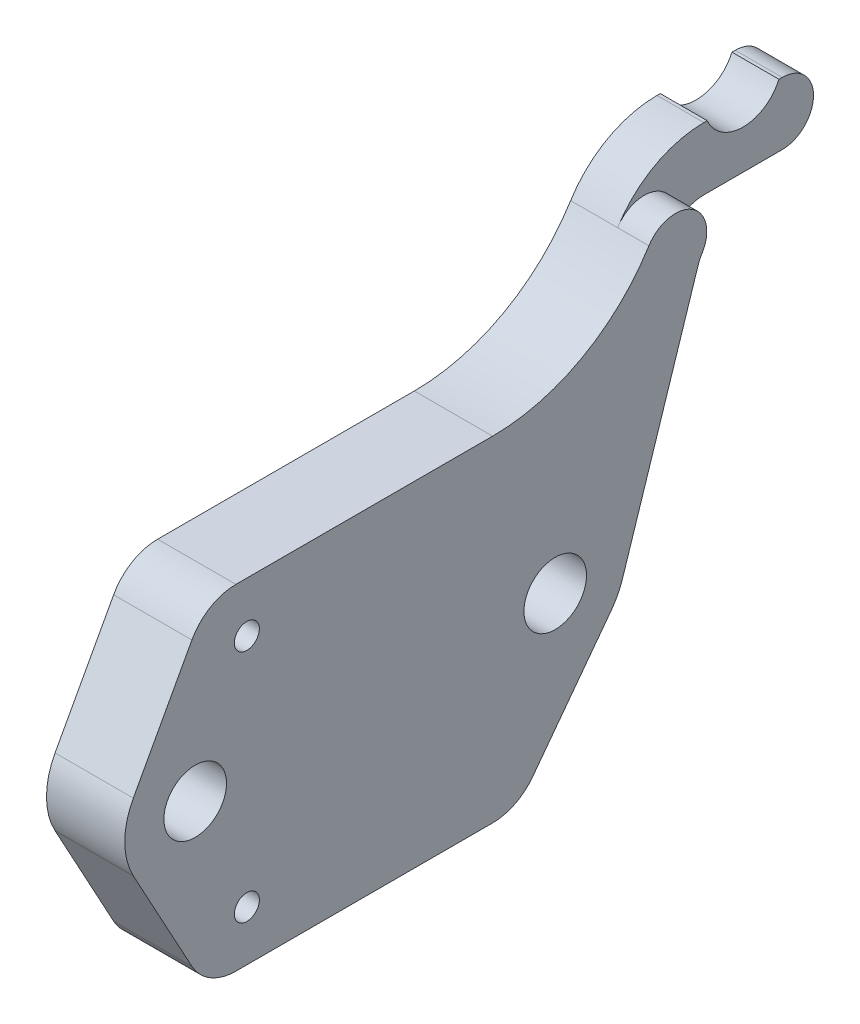
SolidWorks part; units mm, degrees
material "Alliage 1060"
ref_plane "Plan de face" through (0, 0, 0) normal (0, 0, 1) x (1, 0, 0)
ref_plane "Plan de dessus" through (0, 0, 0) normal (0, 1, 0) x (1, 0, 0)
ref_plane "Plan de droite" through (0, 0, 0) normal (1, 0, 0) x (0, 0, -1)
sketch "Esquisse1" plane through (0, 0, 0) normal (0, 0, 1) x (1, 0, 0)
  line L0 (0, 15) -> (0, -15) construction
  line L1 (-2.5, 15) -> (2.5, 15)
  line L2 (-2.5, 15) -> (-2.5, -15)
  line L3 (-2.5, -15) -> (2.5, -15)
  line L4 (2.5, 15) -> (2.5, -15)
  dimension "D1" = 5
  dimension "D2" = 30
extrude "Extrusion1" add sketch "Esquisse1" against normal blind 32.5
sketch "Esquisse2" plane through (2.5, 0, 0) normal (1, 0, 0) x (0, 0, -1)
  line L0 (4.5, -4.3) -> (27.5, -4.3) construction
  line L3 (32.5, -15) -> (0, -15) construction
  line L5 (0, -15) -> (0, 15) construction
  circle A0 centre (4.5, -4.3) radius 2
  circle A1 centre (27.5, -4.3) radius 2
  dimension "D2" = 4
  dimension "D6" = 4
  dimension "D1" = 23
  dimension "D4" = 4.5
  dimension "D5" = 10.7
extrude "Extrusion2" cut sketch "Esquisse2" against normal through all
hole_wizard "Trou taraudé M21" positions "Esquisse10" profile "Esquisse9" tap size "M2" standard "Iso" end condition through all
sketch "Esquisse10" plane through (2.5, 0, 0) normal (1, 0, 0) x (0, 0, -1)
  line L1 (7.8, 3.2) -> (22.8, 3.2)
  line L2 (7.8, 3.2) -> (7.8, -11.8)
  line L3 (7.8, -11.8) -> (22.8, -11.8)
  line L4 (22.8, 3.2) -> (22.8, -11.8)
  line L5 (27.5, -4.3) -> (22.8, -4.3) construction
  circle A0 centre (27.5, -4.3) radius 2 construction
  point P2 (7.8, 3.2)
  point P100 (7.8, -11.8)
  dimension "D1" = 4.7
  dimension "D2" = 15
sketch "Esquisse9" plane through (2.5, 3.2, -7.8) normal (0, 1, 0) x (0, 0, -1)
  line L0 (0, 0) -> (0, 5)
  line L1 (0, 5) -> (0.8, 5)
  line L2 (0.8, 5) -> (0.8, 0)
  line L5 (0.8, 0) -> (0, 0)
  line L11 (0, -6.35) -> (0, 107.95) construction
  dimension "Diamètre du trou pour taraudage jusqu'au prochain" = 1.6
  dimension "Profondeur du trou pour taraudage jusqu'au prochain" = 5
cosmetic thread "Filetage de perçage12" parameters "D2"=2
cosmetic thread "Filetage de perçage13" parameters "D2"=2
sketch "Esquisse14" plane through (-2.5, 0, 0) normal (-1, 0, 0) x (0, 0, 1)
  line L0 (-32.5, 15) -> (-39.2087, 15)
  line L1 (-44, 11) -> (-39, 11)
  line L2 (-36.5348, 8.9159) -> (-32.5, -15)
  line L3 (-32.5, 15) -> (-32.5, -15) construction
  line L4 (-32.5, 15) -> (-32.5, -15)
  line L5 (-43.7913, 15) -> (-44, 15)
  arc A0 (-44, 15) -> (-44, 11) centre (-44, 13) ccw
  arc A1 (-39, 11) -> (-36.5348, 8.9159) centre (-39, 8.5) cw
  arc A2 (-43.7913, 15) -> (-39.2087, 15) centre (-41.5, 16) ccw
  dimension "D3" = 2.5
  dimension "D5" = 2.5
  dimension "D1" = 4
  dimension "D2" = 11.5
  dimension "D4" = 6.5
  dimension "D6" = 2.5
  dimension "D7" = 9
extrude "Boss.-Extru.2" add sketch "Esquisse14" against normal up to surface (5 mm away) up to face at (2.5, 3.2, -8.6)
sketch "Esquisse16" plane through (-2.5, 0, 0) normal (-1, 0, 0) x (0, 0, 1)
  line L0 (0, 15) -> (0, -15) construction
  line L1 (-23.5, -11.8) -> (-7.1, -11.8) construction
  line L2 (-39.2087, 15) -> (0, 15) construction
  line L3 (-32.5, -15) -> (0, -15) construction
  line L4 (-7.1, -11.8) -> (-7.1, 3.2) construction
  line L5 (-7.1, 3.2) -> (-23.5, 3.2) construction
  line L6 (-23.5, 3.2) -> (-23.5, -11.8) construction
  line L7 (0, -4.3) -> (0, -15)
  line L8 (0, -15) -> (-7.1, -15)
  line L9 (-23.5, -15) -> (-32.5, -15)
  line L10 (-32.5, -15) -> (-36.5348, 8.9159)
  line L11 (-39.2087, 15) -> (0, 15) construction
  line L12 (0, -4.3) -> (0, 15)
  line L13 (0, 15) -> (-39, 15)
  line L14 (-0.547, -6.4504) -> (-4.289, -13.3291)
  line L15 (-26.06, -13.72) -> (-31.1, -7)
  line L16 (-31.7814, -5.6856) -> (-36.6215, 9.2698)
  line L17 (-0.547, -2.1496) -> (-4.289, 4.7291)
  line L18 (-7.1, 6.4) -> (-23.5, 6.4)
  arc A0 (-0.547, -6.4504) -> (-0.547, -2.1496) centre (-4.5, -4.3) ccw
  arc A1 (-31.7814, -5.6856) -> (-31.1, -7) centre (-27.5, -4.3) ccw
  arc A2 (-7.1, -15) -> (-4.289, -13.3291) centre (-7.1, -11.8) ccw
  arc A3 (-26.06, -13.72) -> (-23.5, -15) centre (-23.5, -11.8) ccw
  arc A4 (-4.289, 4.7291) -> (-7.1, 6.4) centre (-7.1, 3.2) ccw
  arc A5 (-36.5348, 8.9159) -> (-39, 11) centre (-39, 8.5) ccw construction
  arc A6 (-36.5348, 8.9159) -> (-36.6215, 9.2698) centre (-39, 8.5) ccw
  arc A7 (-33.4849, 11.94) -> (-39, 15) centre (-39, 8.5) ccw
  circle A8 centre (-23.5, 3.2) radius 3.2 construction
  arc A9 (-32.5906, 9.5813) -> (-39, 15) centre (-39, 8.5) ccw construction
  arc A10 (-23.5, 6.4) -> (-33.4849, 11.94) centre (-23.5, 18.168) cw
  arc A12 (-36.5348, 8.9159) -> (-39, 11) centre (-39, 8.5) ccw construction
  point P13 (-7.8, -11.8)
  point P21 (-7.8, 3.2)
  line M5 (0, -15) -> (0, 15)
  line M6 (0, 15) -> (-39.2087, 15)
  arc M11 (-39, 11) -> (-36.5348, 8.9159) centre (-39, 8.5) cw
  line M12 (-36.5348, 8.9159) -> (-32.5, -15)
  line M13 (-32.5, -15) -> (0, -15)
  dimension "D1" = 16.4
  dimension "D2" = 4
extrude "Enlèv. mat.-Extru.3" cut sketch "Esquisse16" against normal through all contours L18 A4 L17 A0 M5 M6 | A2 A0 L14 M13 M5 | A3 L15 A1 L16 M11 M12 M13 region at (-2.5, -8.3467, -31.4965) region at (-2.5, 10.2745, -15.0035) region at (-2.5, -11.8541, -1.8115)
sketch "Esquisse17" plane through (-2.5, 0, 0) normal (1, 0, 0) x (0, 0, -1)
  line L9 (7.1, -15) -> (23.5, -15)
  line L10 (26.06, -13.72) -> (31.1, -7)
  line L11 (31.7814, -5.6856) -> (36.6215, 9.2698)
  line L12 (39, 11) -> (44, 11)
  line L13 (44, 15) -> (43.7913, 15)
  line L14 (39.2087, 15) -> (39, 15)
  line L15 (23.5, 6.4) -> (7.1, 6.4)
  line L16 (4.289, 4.7291) -> (0.547, -2.1496)
  line L17 (0.547, -6.4504) -> (4.289, -13.3291)
  line L18 (7.1, -15) -> (23.5, -15)
  line L19 (26.06, -13.72) -> (31.1, -7)
  line L20 (31.7814, -5.6856) -> (36.6215, 9.2698)
  line L21 (39, 11) -> (44, 11)
  line L22 (44, 15) -> (43.7913, 15)
  line L23 (39.2087, 15) -> (39, 15)
  line L24 (23.5, 6.4) -> (7.1, 6.4)
  line L25 (4.289, 4.7291) -> (0.547, -2.1496)
  line L26 (0.547, -6.4504) -> (4.289, -13.3291)
  arc A0 (36.8788, 9.8231) -> (33.4849, 11.94) centre (35.1819, 10.8815) ccw
  arc A1 (23.5, 6.4) -> (33.4849, 11.94) centre (23.5, 18.168) ccw construction
  arc A2 (39, 11) -> (36.6215, 9.2698) centre (39, 8.5) ccw construction
  arc A13 (23.5, -15) -> (26.06, -13.72) centre (23.5, -11.8) ccw
  arc A14 (31.1, -7) -> (31.7814, -5.6856) centre (27.5, -4.3) ccw
  arc A15 (39, 11) -> (36.6215, 9.2698) centre (39, 8.5) ccw
  arc A16 (44, 11) -> (44, 15) centre (44, 13) ccw
  arc A17 (39.2087, 15) -> (43.7913, 15) centre (41.5, 16) ccw
  arc A18 (39, 15) -> (33.4849, 11.94) centre (39, 8.5) ccw
  arc A19 (23.5, 6.4) -> (33.4849, 11.94) centre (23.5, 18.168) ccw
  arc A20 (7.1, 6.4) -> (4.289, 4.7291) centre (7.1, 3.2) ccw
  arc A21 (0.547, -2.1496) -> (0.547, -6.4504) centre (4.5, -4.3) ccw
  arc A22 (4.289, -13.3291) -> (7.1, -15) centre (7.1, -11.8) ccw
  arc A23 (23.5, -15) -> (26.06, -13.72) centre (23.5, -11.8) ccw
  arc A24 (31.1, -7) -> (31.7814, -5.6856) centre (27.5, -4.3) ccw
  arc A25 (39, 11) -> (36.6215, 9.2698) centre (39, 8.5) ccw
  arc A26 (44, 11) -> (44, 15) centre (44, 13) ccw
  arc A27 (39.2087, 15) -> (43.7913, 15) centre (41.5, 16) ccw
  arc A28 (39, 15) -> (33.4849, 11.94) centre (39, 8.5) ccw
  arc A29 (23.5, 6.4) -> (33.4849, 11.94) centre (23.5, 18.168) ccw
  arc A30 (7.1, 6.4) -> (4.289, 4.7291) centre (7.1, 3.2) ccw
  arc A31 (0.547, -2.1496) -> (0.547, -6.4504) centre (4.5, -4.3) ccw
  arc A32 (4.289, -13.3291) -> (7.1, -15) centre (7.1, -11.8) ccw
  arc M79 (33.4849, 11.94) -> (39, 15) centre (39, 8.5) cw
  line M80 (39, 15) -> (39.2087, 15)
  arc M81 (39.2087, 15) -> (43.7913, 15) centre (41.5, 16) ccw
  line M82 (43.7913, 15) -> (44, 15)
  arc M83 (44, 15) -> (44, 11) centre (44, 13) cw
  line M84 (44, 11) -> (39, 11)
  arc M85 (39, 11) -> (36.6215, 9.2698) centre (39, 8.5) ccw
  dimension "D1" = 0
extrude "Enlèv. mat.-Extru.4" cut sketch "Esquisse17" along normal through all from offset 3 contours A0 M85 M79 M80 M81 M82 M83 M84 region at (-2.5, 12.7937, -40.6492)
